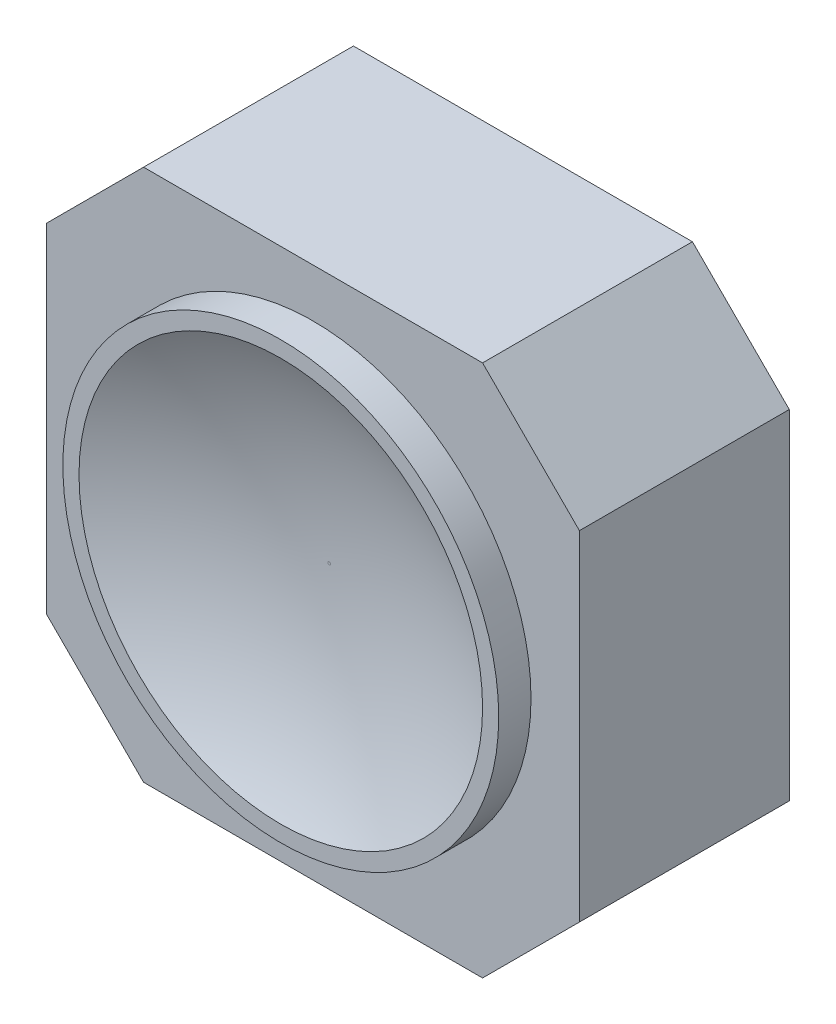
SolidWorks part; units mm, degrees
ref_plane "Front Plane" through (0, 0, 0) normal (0, 0, 1) x (1, 0, 0)
ref_plane "Top Plane" through (0, 0, 0) normal (0, 1, 0) x (1, 0, 0)
ref_plane "Right Plane" through (0, 0, 0) normal (1, 0, 0) x (0, 0, -1)
sketch "Sketch1" plane through (0, 0, 0) normal (0, 0, 1) x (1, 0, 0)
  line L0 (-8.25, -5.25) -> (-5.25, -8.25)
  line L1 (-5.25, 8.25) -> (5.25, 8.25)
  line L2 (-8.25, 5.25) -> (-8.25, -5.25)
  line L3 (-5.25, -8.25) -> (5.25, -8.25)
  line L4 (8.25, 5.25) -> (8.25, -5.25)
  line L5 (5.25, -8.25) -> (8.25, -5.25)
  line L6 (5.25, 8.25) -> (8.25, 5.25)
  line L7 (-8.25, 5.25) -> (-5.25, 8.25)
  point P0 (-8.25, 8.25)
  point P1 (8.25, -8.25)
  point P2 (-8.25, -8.25)
  point P3 (8.25, 8.25)
  dimension "D1" = 16.5
  dimension "D2" = 16.5
  dimension "D3" = 8.25
  dimension "D4" = 8.25
extrude "Boss-Extrude2" add sketch "Sketch1" along normal blind 6.5
sketch "Sketch2" plane through (0, 0, 6.5) normal (0, 0, 1) x (1, 0, 0)
  circle A0 centre (0, 0) radius 6.25
  dimension "D1" = 12.5
extrude "Cut-Extrude1" cut sketch "Sketch2" against normal blind 0.5
sketch "Sketch3" plane through (0, 0, 0) normal (0, 0, -1) x (-1, 0, 0)
  circle A0 centre (0, 0) radius 6.5
  dimension "D1" = 13
sketch "Sketch8" plane through (0, 0, 6.5) normal (0, 0, 1) x (1, 0, 0)
  circle A0 centre (0, 0) radius 6.25
  circle A1 centre (0, 0) radius 6.75
  dimension "D1" = 0.5
  dimension "D2" = 12.5
extrude "Boss-Extrude6" add sketch "Sketch8" along normal blind 1
fillet "Fillet5" radius 13.6 1 edges at (6.25, 0, 6)
extrude "Cut-Extrude2" cut sketch "Sketch3" against normal blind 3
sketch "Sketch9" plane through (0, 0, 3) normal (0, 0, -1) x (-1, 0, 0)
  line L0 (0, 10.4647) -> (0, -11.9799) construction
  line L1 (-7.2075, 1.375) -> (-3.25, 1.375)
  line L2 (-7.2075, 1.375) -> (-7.2075, -1.375)
  line L3 (-7.2075, -1.375) -> (-3.25, -1.375)
  line L4 (-3.25, 1.375) -> (-3.25, -1.375)
  line L5 (3.25, 1.375) -> (3.25, -1.375)
  line L6 (7.2075, -1.375) -> (3.25, -1.375)
  line L7 (7.2075, 1.375) -> (7.2075, -1.375)
  line L8 (7.2075, 1.375) -> (3.25, 1.375)
  dimension "D1" = 2.75
  dimension "D2" = 1.375
  dimension "D3" = 3.25
extrude "Boss-Extrude7" add sketch "Sketch9" along normal blind 3
